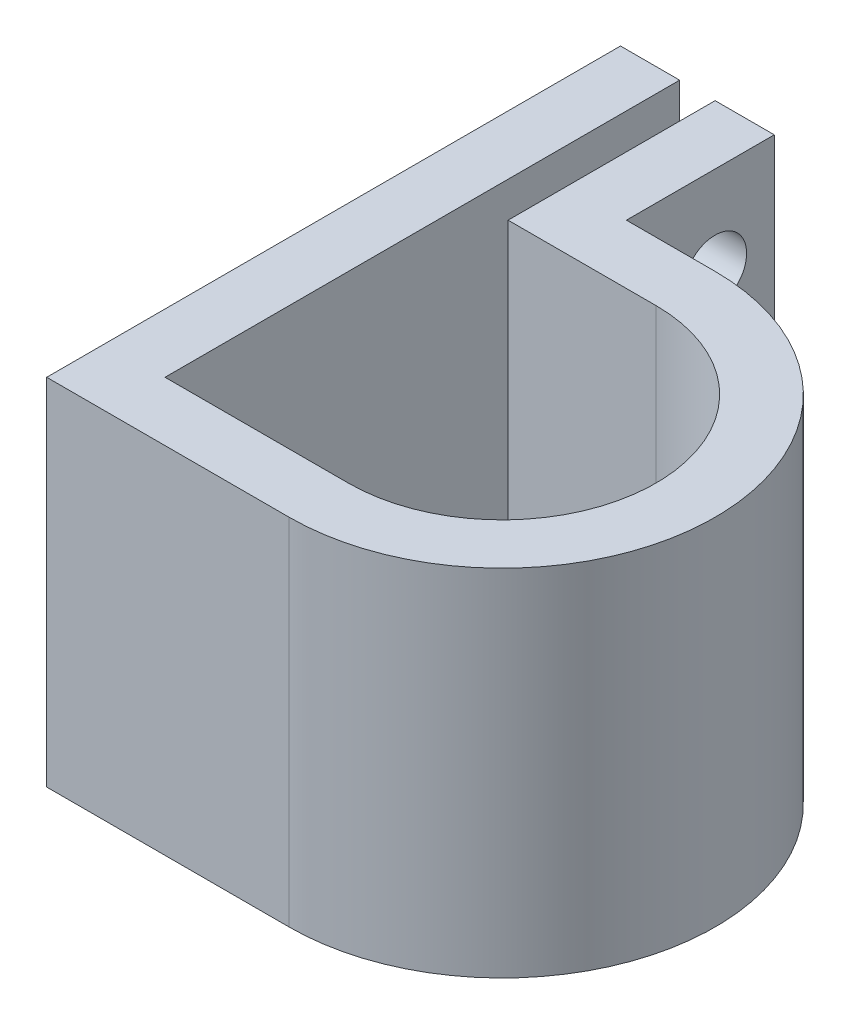
SolidWorks part; units mm, degrees
ref_plane "Front Plane" through (0, 0, 0) normal (0, 0, 1) x (1, 0, 0)
ref_plane "Top Plane" through (0, 0, 0) normal (0, 1, 0) x (1, 0, 0)
ref_plane "Right Plane" through (0, 0, 0) normal (1, 0, 0) x (0, 0, -1)
sketch "Sketch1" plane through (0, 0, 0) normal (0, 1, 0) x (1, 0, 0)
  line L0 (0, -16.51) -> (-19.685, -16.51)
  line L1 (-19.685, -16.51) -> (-19.685, 38.735)
  line L2 (0, 16.51) -> (-15.875, 16.51)
  line L3 (-15.875, 16.51) -> (-15.875, 38.735)
  line L4 (-18.9865, 15.1759) -> (-15.875, 15.1759) construction
  line L5 (-18.9865, 15.1759) -> (-18.9865, -16.0033) construction
  line L6 (-18.9865, -16.0033) -> (-15.875, -16.0033) construction
  line L7 (-15.875, 15.1759) -> (-15.875, -16.0033) construction
  line L8 (-15.875, 38.735) -> (-19.685, 38.735) construction
  line L9 (-15.875, 38.735) -> (-9.525, 38.735)
  line L10 (-9.525, 38.735) -> (-9.525, 22.86)
  line L11 (-9.525, 22.86) -> (0, 22.86)
  line L12 (0, -22.86) -> (-26.035, -22.86)
  line L13 (-26.035, -22.86) -> (-26.035, 38.735)
  line L14 (-26.035, 38.735) -> (-19.685, 38.735)
  arc A0 (0, 16.51) -> (0, -16.51) centre (0, 0) cw
  circle A1 centre (0, 0) radius 15.875 construction
  arc A2 (0, 22.86) -> (0, -22.86) centre (0, 0) cw
  point P18 (0, 0)
  point P21 (-19.685, 32.2891)
  dimension "D1" = 16.51
  dimension "D4" = 31.75
  dimension "D2" = 19.685
  dimension "D3" = 6.35
  dimension "D5" = 15.875
  dimension "D6" = 3.1115
  dimension "D7" = 22.225
  dimension "D8" = 6.35
  dimension "D9" = 6.35
  dimension "D10" = 15.875
  dimension "D11" = 3.81
extrude "Boss-Extrude1" add sketch "Sketch1" along normal blind 38.1
sketch "Sketch2" plane through (-9.525, 0, 0) normal (1, 0, 0) x (0, 0, -1)
  line L1 (22.86, 38.1) -> (38.735, 38.1) construction
  line L2 (38.735, 38.1) -> (38.735, 0) construction
  line L3 (22.86, 0) -> (38.735, 0) construction
  circle A0 centre (32.385, 28.575) radius 3.3782
  circle A1 centre (32.385, 9.525) radius 3.3782
  dimension "D1" = 6.7564
  dimension "D2" = 9.525
  dimension "D3" = 6.35
  dimension "D4" = 19.05
  dimension "D5" = 9.525
extrude "Cut-Extrude1" cut sketch "Sketch2" against normal through all
